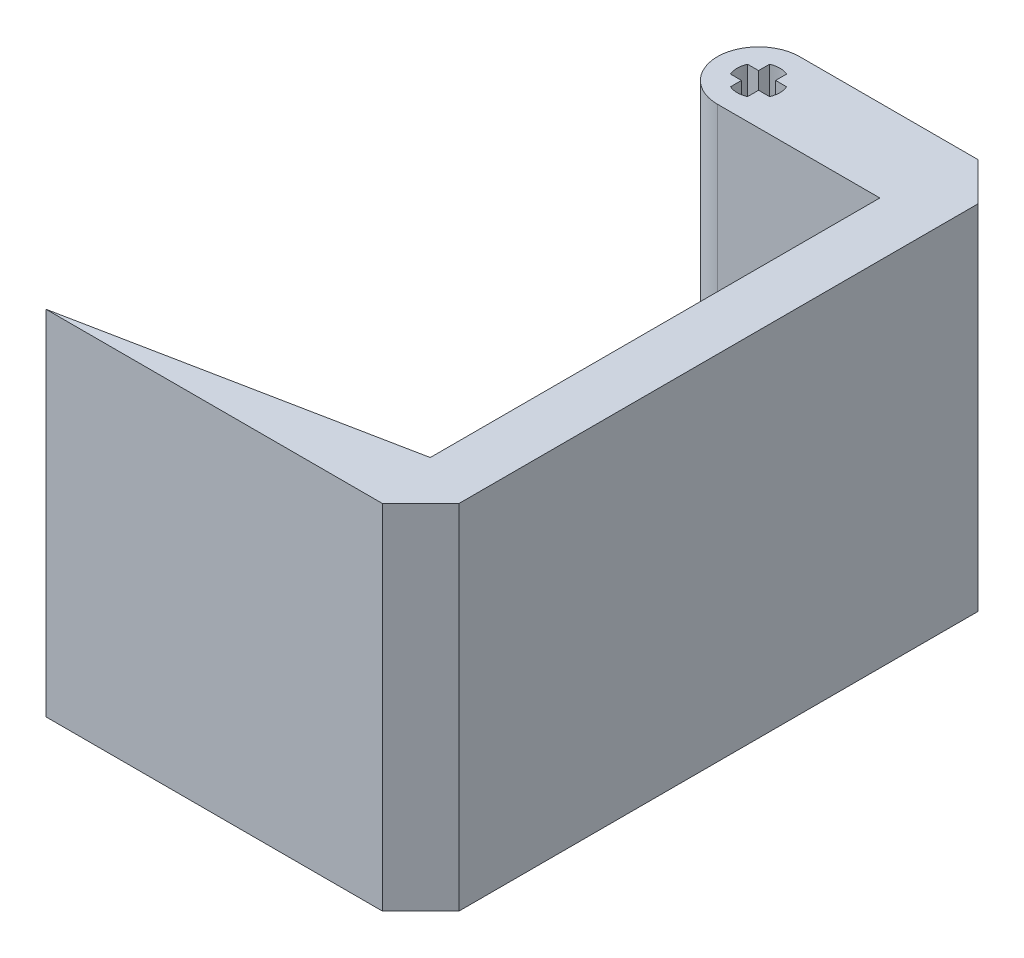
SolidWorks part; units mm, degrees
ref_plane "Front Plane" through (0, 0, 0) normal (0, 0, 1) x (1, 0, 0)
ref_plane "Top Plane" through (0, 0, 0) normal (0, 1, 0) x (1, 0, 0)
ref_plane "Right Plane" through (0, 0, 0) normal (1, 0, 0) x (0, 0, -1)
sketch "Sketch1" plane through (0, 0, 0) normal (0, 1, 0) x (1, 0, 0)
  line L0 (-1, 1) -> (-2.2913, 1)
  line L1 (-1, -1) -> (-2.2913, -1)
  line L2 (1, 1) -> (1, 2.2913)
  line L3 (-1, 1) -> (-1, 2.2913)
  line L4 (1, -1) -> (2.2913, -1)
  line L5 (1, 1) -> (2.2913, 1)
  line L6 (-1, -1) -> (-1, -2.2913)
  line L7 (1, -1) -> (1, -2.2913)
  line L8 (25.4, 4.826) -> (0, 4.826)
  line L9 (19.05, -4.826) -> (0, -4.826)
  line L10 (25.4, 4.826) -> (25.4, -65.024)
  line L11 (25.4, -65.024) -> (-18.542, -65.024)
  line L12 (-18.542, -65.024) -> (19.05, -57.5506)
  line L13 (19.05, -57.5506) -> (19.05, -4.826)
  arc A0 (-2.2913, 1) -> (-2.2913, -1) centre (0, 0) ccw
  arc A1 (1, 2.2913) -> (-1, 2.2913) centre (0, 0) ccw
  arc A2 (2.2913, -1) -> (2.2913, 1) centre (0, 0) ccw
  arc A3 (-1, -2.2913) -> (1, -2.2913) centre (0, 0) ccw
  arc A4 (0, -4.826) -> (0, 4.826) centre (0, 0) cw
  point P13 (0, 0)
  dimension "D1" = 5
  dimension "D7" = 4.826
  dimension "D8" = 57.5506
  dimension "D2" = 1
  dimension "D3" = 6.35
  dimension "D4" = 69.85
  dimension "D5" = 25.4
  dimension "D6" = 43.942
extrude "Boss-Extrude6" add sketch "Sketch1" along normal blind 41.402
sketch "Sketch2" plane through (0, 0, 0) normal (0, 1, 0) x (1, 0, 0)
  line L0 (25.4, -60.5339) -> (20.9099, -65.024)
  line L1 (25.4, -65.024) -> (25.4, 4.826) construction
  line L2 (-18.542, -65.024) -> (25.4, -65.024) construction
  line L3 (25.4, 0.3359) -> (20.9099, 4.826)
  line L4 (25.4, 4.826) -> (0, 4.826) construction
  line L8 (25.4, -60.5339) -> (25.4, -65.024)
  line L9 (20.9099, -65.024) -> (25.4, -65.024)
  line L10 (20.9099, 4.826) -> (25.4, 4.826)
  line L11 (25.4, 4.826) -> (25.4, 0.3359)
  dimension "D1" = 6.35
extrude "Cut-Extrude1" cut sketch "Sketch2" along normal through all
sketch "Sketch4" plane through (0, 0, 0) normal (0, -1, 0) x (1, 0, 0)
  line L5 (24.3815, 29.3748) -> (24.3815, 26.4035)
  line L6 (24.3815, 26.4035) -> (22.0896, 26.4035)
  line L7 (22.1181, 31.585) -> (22.1039, 33.88)
  arc A0 (19.7802, 26.4035) -> (22.0896, 26.4035) centre (20.9349, 27.5582) cw
  arc A1 (22.1181, 31.585) -> (22.1039, 31.5994) centre (23.2728, 32.7397) cw
  arc A2 (19.7802, 31.585) -> (22.1039, 33.88) centre (20.9349, 32.7397) cw
  arc A3 (22.1179, 31.614) -> (22.0896, 31.585) centre (20.9349, 32.7397) cw
  arc A4 (22.1039, 33.88) -> (24.4276, 31.585) centre (23.2728, 32.7397) cw
